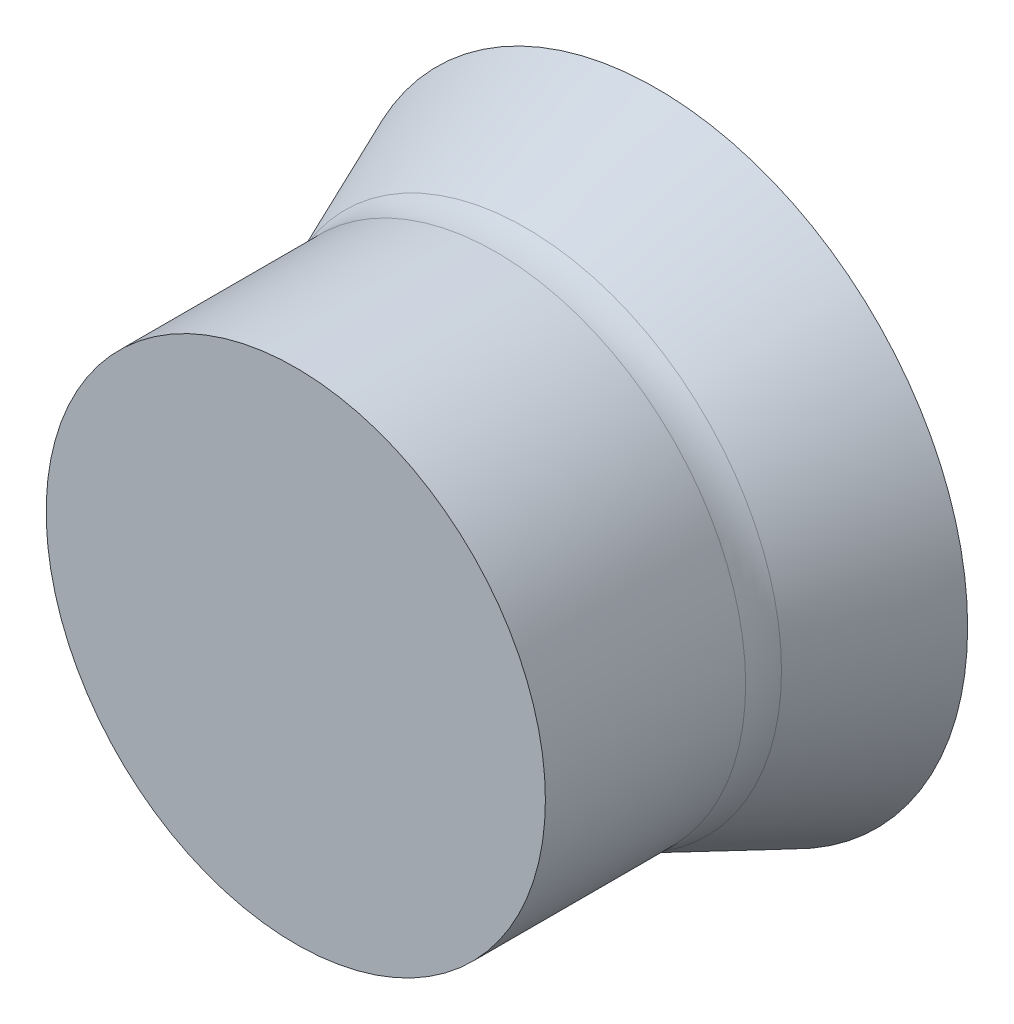
SolidWorks part; units mm, degrees
ref_plane "Front Plane" through (0, 0, 0) normal (0, 0, 1) x (1, 0, 0)
ref_plane "Top Plane" through (0, 0, 0) normal (0, 1, 0) x (1, 0, 0)
ref_plane "Right Plane" through (0, 0, 0) normal (1, 0, 0) x (0, 0, -1)
sketch "Sketch1" plane through (0, 0, 0) normal (0, 1, 0) x (1, 0, 0)
  line L0 (0, -34.925) -> (34.925, -34.925)
  line L1 (-23.1775, -34.925) -> (23.1775, -34.925) construction
  line L2 (34.925, -34.925) -> (34.925, 0)
  line L3 (34.925, 0) -> (37.465, 0)
  line L4 (37.465, 0) -> (46.6729, 16.7019)
  line L5 (46.6729, 16.7019) -> (38.371, -2.94)
  line L6 (37.465, -7.4107) -> (37.465, -37.465)
  line L7 (37.465, -37.465) -> (0, -37.465)
  line L8 (0, -37.465) -> (0, -34.925)
  arc A0 (38.371, -2.94) -> (37.465, -7.4107) centre (48.9484, -7.4107) ccw
  point P12 (0, 0)
  point P15 (0, 0)
  point P16 (38.371, -2.94)
  dimension "D1" = 2.54
  dimension "D3" = 11.4834
  dimension "D2" = 2.54
  dimension "D4" = 2.94
revolve "Revolve1" add sketch "Sketch1" angle 360 about L8
